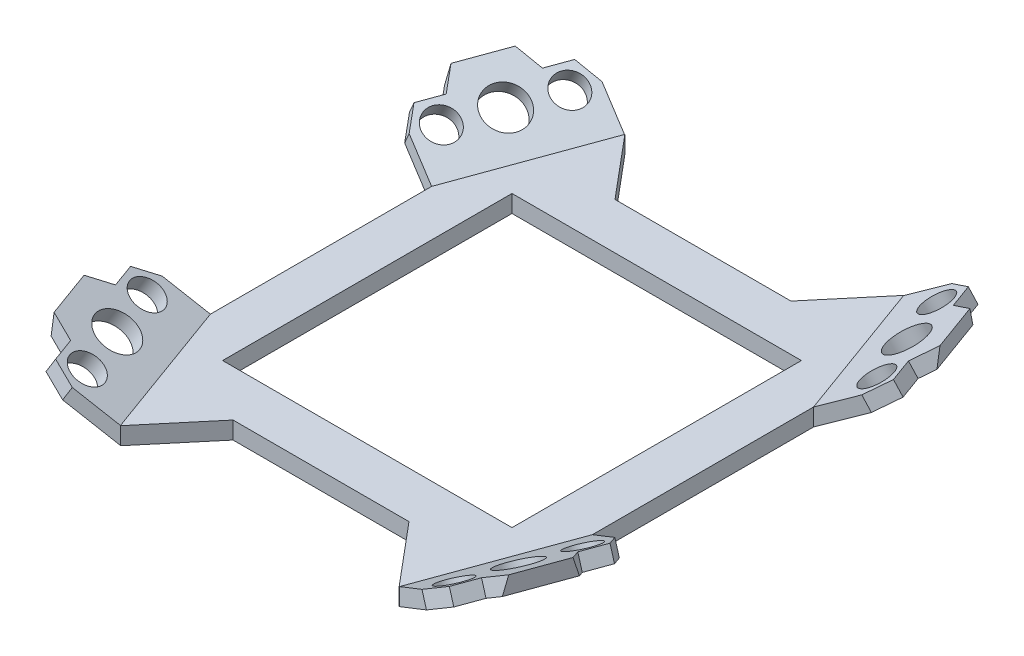
SolidWorks part; units mm, degrees
ref_plane "Front Plane" through (0, 0, 0) normal (0, 0, 1) x (1, 0, 0)
ref_plane "Top Plane" through (0, 0, 0) normal (0, 1, 0) x (1, 0, 0)
ref_plane "Right Plane" through (0, 0, 0) normal (1, 0, 0) x (0, 0, -1)
sketch "Sketch11" plane through (0, 0, 0) normal (0, 1, 0) x (1, 0, 0)
  line L0 (-50, -50) -> (-50, 50)
  line L1 (-30.4059, -66) -> (30.4059, -66)
  line L2 (-66, -38.2239) -> (-66, 0)
  line L3 (-30.4059, 66) -> (30.4059, 66)
  line L4 (66, -38.2239) -> (66, 38.2239)
  line L5 (-66, -66) -> (66, 66) construction
  line L6 (-50, 50) -> (66, -66) construction
  line L7 (-50, 50) -> (50, 50)
  line L8 (50, -50) -> (50, 50)
  line L9 (-50, -50) -> (50, -50)
  line L18 (-66, 0) -> (-66, 38.2239) construction
  line L19 (-66, -66) -> (-66, 66) construction
  line L20 (66, 38.2239) -> (66, 66) construction
  line L21 (66, -66) -> (66, 66) construction
  line L22 (66, -66) -> (66, -38.2239) construction
  line L23 (-66, -66) -> (-66, -38.2239) construction
  line L24 (-48.1804, 87.1828) -> (-65.9654, 38.3188)
  line L27 (-48.1804, 87.1828) -> (-30.4059, 66)
  line L28 (-66, 38.2239) -> (-66, 66) construction
  line L29 (-66, 66) -> (66, 66) construction
  line L30 (0, -55) -> (0, 55) construction
  line L31 (48.1804, 87.1828) -> (30.4059, 66)
  line L32 (65.9654, 38.3188) -> (66, 38.2239)
  line L33 (48.1804, 87.1828) -> (65.9654, 38.3188)
  line L34 (-55, 0) -> (55, 0) construction
  line L35 (65.9654, -38.3188) -> (66, -38.2239)
  line L36 (48.1804, -87.1828) -> (65.9654, -38.3188)
  line L37 (48.1804, -87.1828) -> (30.4059, -66)
  line L38 (-48.1804, -87.1828) -> (-30.4059, -66)
  line L39 (-65.9654, -38.3188) -> (-66, -38.2239)
  line L40 (-48.1804, -87.1828) -> (-65.9654, -38.3188)
  line L41 (30.4059, 66) -> (66, 66) construction
  line L42 (30.4059, -66) -> (66, -66) construction
  line L43 (-66, -66) -> (66, -66) construction
  line L44 (-66, -66) -> (-30.4059, -66) construction
  line L45 (-66, 66) -> (-30.4059, 66) construction
  line L46 (-57.0729, 62.7508) -> (-66, 66) construction
  line L47 (-66, 38.2239) -> (-66, 0)
  line L48 (-66, 38.2239) -> (-65.9654, 38.3188)
  point P0 (0, 0)
  dimension "D1" = 132
  dimension "D2" = 9.5
  dimension "D4" = 52
  dimension "D5" = 60
  dimension "D8" = 20
  dimension "D3" = 16
extrude "Boss-Extrude6" add sketch "Sketch11" along normal blind 6
ref_plane "Plane1" through (4.5644, 0, -12.5405) normal (0.342, 0, -0.9397) x (0, -1, 0)
sketch "Sketch12" plane through (4.5644, 0, -12.5405) normal (0.342, 0, -0.9397) x (0, -1, 0)
  line L0 (-6, 75.093) -> (-21, 101.0738)
  line L1 (-21, 101.0738) -> (-15, 101.0738)
  line L2 (-15, 101.0738) -> (0, 75.093)
  line L4 (-6, 75.093) -> (0, 75.093)
  point P2 (0, 0)
  point P3 (0, 0)
  point P6 (0, 0)
  point P7 (0, 0)
  point P8 (0, 0)
  point P9 (0, 0)
  dimension "D1" = 6
  dimension "D2" = 30
  dimension "D3" = 60
extrude "Boss-Extrude7" add sketch "Sketch12" along normal blind 52
sketch "Sketch13" plane through (-15.1997, -28.0162, -5.5322) normal (0.4698, 0.866, 0.171) x (0.8827, -0.4609, -0.091)
  line L0 (-51.2289, 92.4122) -> (-71.3763, 44.4738) construction
  line L1 (-65.0573, 98.2239) -> (-37.4005, 86.6004) construction
  line L2 (-85.2046, 50.2856) -> (-57.5479, 38.6621) construction
  line L3 (-65.0573, 98.2239) -> (-85.2046, 50.2856) construction
  line L5 (-71.7755, 82.2385) -> (-85.1655, 50.3787) construction
  line L6 (-78.4863, 66.2709) -> (-73.2618, 59.3889)
  line L15 (-73.2618, 59.3889) -> (-76.6247, 51.3873)
  line L16 (-76.6247, 51.3873) -> (-71.3763, 44.4738)
  line L17 (-51.2289, 92.4122) -> (-59.8399, 91.3237)
  line L24 (-71.7755, 82.2385) -> (-63.2027, 83.3222)
  line L25 (-63.2027, 83.3222) -> (-59.8399, 91.3237)
  line L37 (-71.3763, 44.4738) -> (-85.2046, 50.2856)
  line L38 (-85.2046, 50.2856) -> (-78.4863, 66.2709)
  line L39 (-71.7755, 82.2385) -> (-65.0573, 98.2239)
  line L40 (-65.0573, 98.2239) -> (-51.2289, 92.4122)
  line L41 (-85.1655, 50.3787) -> (-78.4863, 66.2709) construction
  line L49 (-44.1188, 70.6151) -> (-49.3553, 77.5128) [skipped]
  line L51 (-60.0486, 83.7209) -> (-71.7755, 82.2385) [skipped]
  line L52 (-81.8532, 58.3033) -> (-86.159, 57.7591) construction
  line L53 (-54.1654, 46.6668) -> (-56.7896, 50.1235) construction
  line L54 (-62.7648, 45.5623) -> (-61.0832, 49.5633) [skipped]
  line L55 (-71.3763, 44.4738) -> (-62.7648, 45.5623) [skipped]
  line L56 (-68.0134, 52.4754) -> (-62.5566, 53.1651) construction
  line L57 (-50.8296, 54.6474) -> (-44.1188, 70.6151) [skipped]
  circle A0 centre (-68.0132, 52.4758) radius 5.5
  circle A1 centre (-61.3026, 68.443) radius 7
  circle A2 centre (-54.592, 84.4101) radius 5.5
  dimension "D1" = 11
  dimension "D2" = 11
  dimension "D3" = 14
  dimension "D6" = 17.3397
  dimension "D4" = 17.32
  dimension "D5" = 17.32
  dimension "D7" = 17.3397
  dimension "D8" = 120
  dimension "D9" = 30
  dimension "D10" = 7.4833
  dimension "D11" = 30
extrude "Cut-Extrude1" cut sketch "Sketch13" against normal through all
mirror "Mirror3" about plane through (0, 0, 0) normal (1, 0, 0) of "Cut-Extrude1", "Boss-Extrude7"
mirror "Mirror4" about plane through (0, 0, 0) normal (0, 0, 1) of "Boss-Extrude7", "Cut-Extrude1", "Mirror3"
